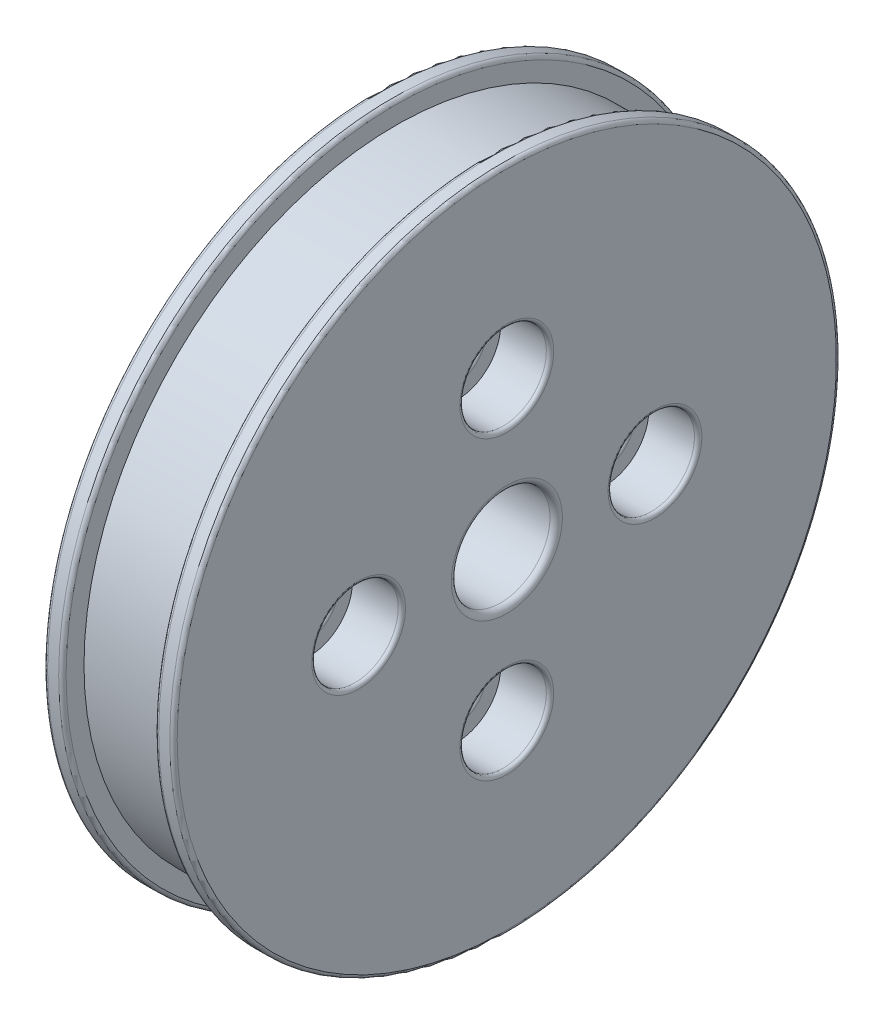
SolidWorks part; units mm, degrees
ref_plane "Front Plane" through (0, 0, 0) normal (0, 0, 1) x (1, 0, 0)
ref_plane "Top Plane" through (0, 0, 0) normal (0, 1, 0) x (1, 0, 0)
ref_plane "Right Plane" through (0, 0, 0) normal (1, 0, 0) x (0, 0, -1)
sketch "Sketch1" plane through (0, 0, 0) normal (0, 1, 0) x (1, 0, 0)
  line L0 (0, 0) -> (5.179, 0) construction
  line L1 (0, 0) -> (0, 4) construction
  line L2 (0, 4) -> (0, 27)
  line L3 (0, 27) -> (1.5, 27)
  line L4 (1.5, 27) -> (1.5, 25.25)
  line L5 (1.5, 25.25) -> (9, 25.25)
  line L6 (9, 25.25) -> (9, 27)
  line L7 (9, 27) -> (10.5, 27)
  line L8 (10.5, 27) -> (10.5, 17.5)
  line L11 (10.5, 4) -> (0, 4)
  line L12 (10.5, 17.5) -> (10.5, 4)
  dimension "D1" = 4
  dimension "D2" = 10.5
  dimension "54/2" = 27
  dimension "D3" = 25.25
  dimension "D6" = 7.5
revolve "Revolve1" add sketch "Sketch1" angle 360 about L0
fillet "Fillet1" radius 0.3 5 edges at (0, 0, 4) (0, 0, 27) (1.5, 0, 27) (9, 0, 27) (10.5, 0, 27)
sketch "Sketch2" plane through (10.5, 0, 0) normal (1, 0, 0) x (0, 0, -1)
  circle A0 centre (0, 0) radius 12
  circle A1 centre (-12, 0) radius 2
  circle A2 centre (-12, 0) radius 3.5
  circle A3 centre (0, 12) radius 3.5
  circle A4 centre (0, 12) radius 2
  circle A5 centre (12, 0) radius 3.5
  circle A6 centre (12, 0) radius 2
  circle A7 centre (0, -12) radius 3.5
  circle A8 centre (0, -12) radius 2
  point P18 (0, 0)
  dimension "D1" = 24
  dimension "D2" = 4
  dimension "D3" = 7
  dimension "D4" = 4
extrude "Cut-Extrude1" cut sketch "Sketch2" against normal through all contours A1 | A4 | A6 | A8
extrude "Cut-Extrude2" cut sketch "Sketch2<3>" against normal blind 4 contours A2 | A7 | A5 | A3
sketch "Sketch2<3>" plane through (10.5, 0, 0) normal (1, 0, 0) x (0, 0, -1) same geometry as "Sketch2"
fillet "Fillet2" radius 0.3 12 edges at (6.5, -12, -2) (10.5, -12, -3.5) (6.5, 0, -14) (10.5, 0, -15.5) (6.5, 0, 10) (10.5, 0, 8.5) (6.5, 12, -2) (10.5, 12, -3.5) (0, 12, -2) (0, 0, -14) (0, 0, 10) (0, -12, -2)
fillet "Fillet3" radius 0.5 1 edges at (10.5, 0, 4)
